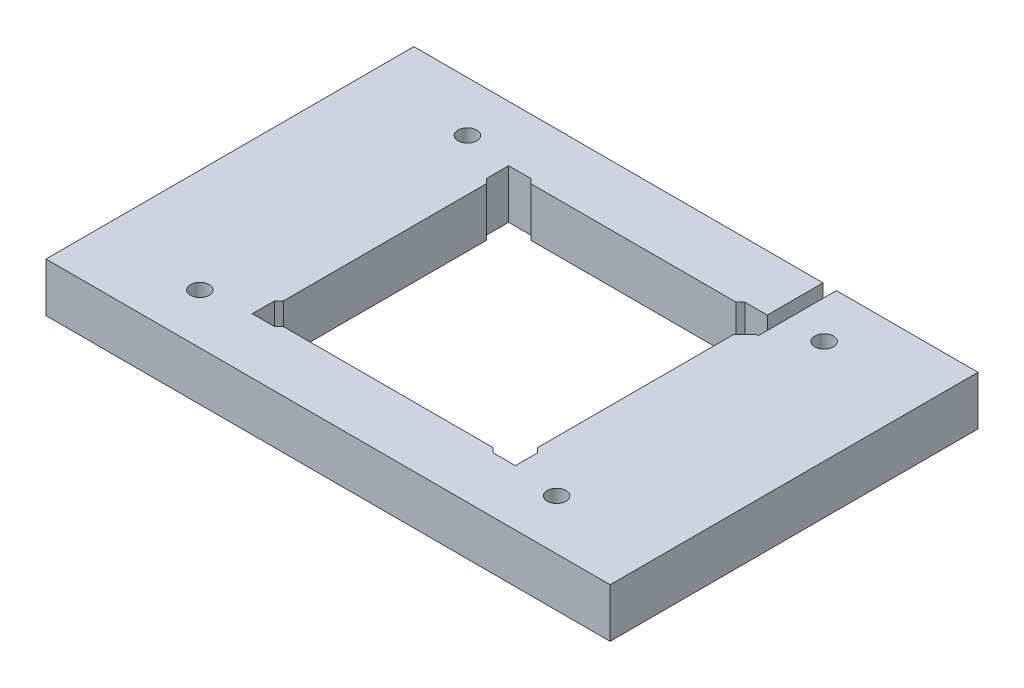
SolidWorks part; units mm, degrees
ref_plane "Спереди" through (0, 0, 0) normal (0, 0, 1) x (1, 0, 0)
ref_plane "Сверху" through (0, 0, 0) normal (0, 1, 0) x (1, 0, 0)
ref_plane "Справа" through (0, 0, 0) normal (1, 0, 0) x (0, 0, -1)
sketch "Эскиз1" plane through (0, 0, 0) normal (0, 1, 0) x (1, 0, 0)
  line L6 (31.5, 27.75) -> (31.5, 41.25)
  line L8 (-63.25, -41.25) -> (-63.25, 41.25)
  line L10 (63.25, 41.25) -> (63.25, -41.25)
  line L11 (-63.25, -41.25) -> (63.25, -41.25)
  line L13 (31.5, 27.75) -> (31.5, 23.75)
  line L14 (31.5, 23.75) -> (28.5, 23.75)
  line L16 (-63.25, 41.25) -> (28.5, 41.25)
  line L17 (31.5, 41.25) -> (63.25, 41.25)
  line L18 (-29.5, 28.75) -> (-24.5, 28.75)
  line L19 (-24.5, 28.75) -> (-24.5, 27.75)
  line L20 (-29.5, 28.75) -> (-29.5, 23.75)
  line L21 (-29.5, 23.75) -> (-28.5, 23.75)
  line L22 (29.5, -28.75) -> (29.5, -23.75)
  line L23 (28.5, -23.75) -> (29.5, -23.75)
  line L24 (-29.5, -28.75) -> (-24.5, -28.75)
  line L25 (-29.5, -23.75) -> (-29.5, -28.75)
  line L26 (-24.5, -28.75) -> (-24.5, -27.75)
  line L27 (-29.5, -23.75) -> (-28.5, -23.75)
  line L28 (24.5, -28.75) -> (24.5, -27.75)
  line L29 (29.5, -28.75) -> (24.5, -28.75)
  line L30 (28.5, 28.75) -> (23.5, 28.75)
  line L31 (23.5, 28.75) -> (23.5, 27.75)
  line L32 (-24.5, 27.75) -> (23.5, 27.75)
  line L33 (-28.5, 23.75) -> (-28.5, -23.75)
  line L34 (-24.5, -27.75) -> (24.5, -27.75)
  line L35 (28.5, -23.75) -> (28.5, 23.75)
  line L36 (28.5, 28.75) -> (28.5, 41.25)
  circle A0 centre (-40, 30) radius 2.1
  circle A1 centre (40, 30) radius 2.1
  circle A2 centre (40, -30) radius 2.1
  circle A3 centre (-40, -30) radius 2.1
extrude "Бобышка-Вытянуть2" add sketch "Эскиз1" along normal blind 11
chamfer "Фаска1" distance 2.5 angle 45 1 edges at (28.5, 5.5, -23.75)
chamfer "Фаска2" distance 1 angle 45 7 edges at (23.5, 5.5, -27.75) (28.5, 5.5, 23.75) (24.5, 5.5, 27.75) (-24.5, 5.5, 27.75) (-28.5, 5.5, 23.75) (-28.5, 5.5, -23.75) (-24.5, 5.5, -27.75)
